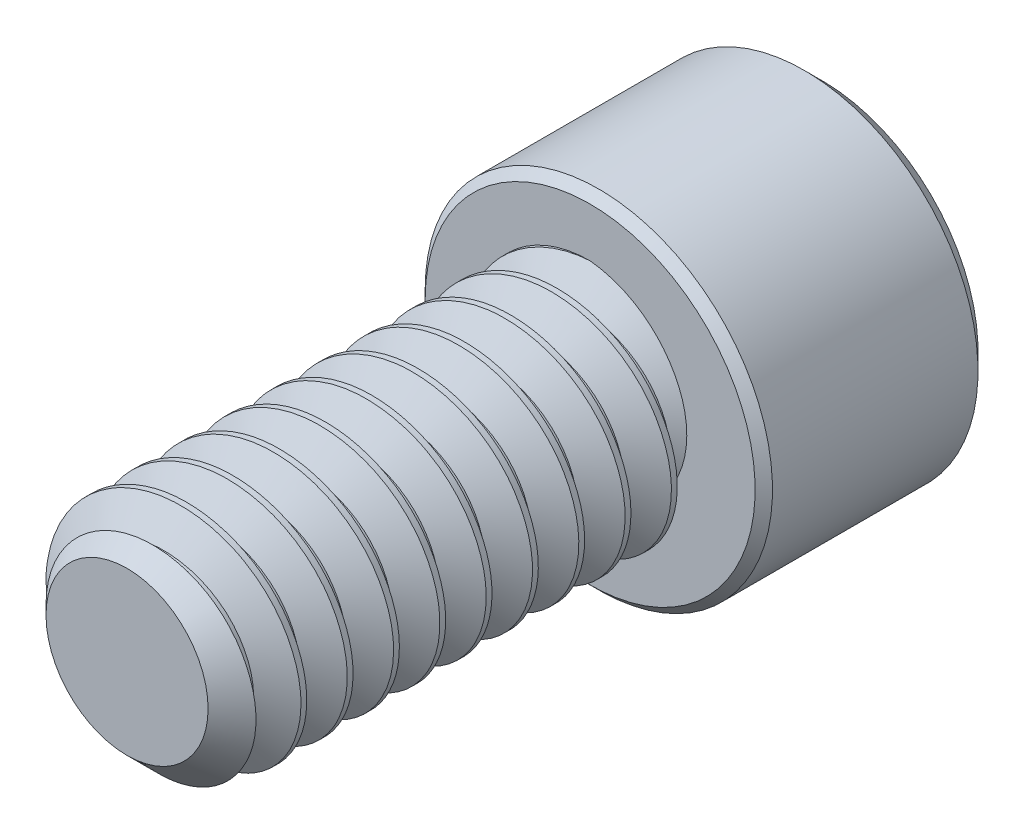
SolidWorks part; units mm, degrees
ref_plane "Front Plane" through (0, 0, 0) normal (0, 0, 1) x (1, 0, 0)
ref_plane "Top Plane" through (0, 0, 0) normal (0, 1, 0) x (1, 0, 0)
ref_plane "Right Plane" through (0, 0, 0) normal (1, 0, 0) x (0, 0, -1)
sketch "Sketch0" plane through (0, 0, 0) normal (1, 0, 0) x (0, 0, -1)
  line L0 (0, 0) -> (12.7, 0) construction
  point P2 (19.05, 0)
  point P4 (0, 0)
  dimension "D1" = 12.7
  dimension "D2" = 6.35
  dimension "Min Thread" = 0
sketch "Sketch1" plane through (0, 0, 0) normal (0, 0, 1) x (1, 0, 0)
  circle A0 centre (0, 0) radius 3.175
  dimension "OD" = 6.35
extrude "Extrude1" add sketch "Sketch1" against normal blind 12.7
sketch "Sketch2" plane through (0, 0, 0) normal (0, 0, 1) x (1, 0, 0)
  circle A0 centre (0, 0) radius 3.175 construction
  circle A1 centre (0, 0) radius 3.175
curve "Helix/Spiral1" pitch 1.27 height 13.97 turns 11 parameters "pitch"=1.27
chamfer "Chamfer3" distance 0.9525 angle 45 1 edges at (3.175, 0, 0)
sketch "Sketch3" plane through (0, 0, 0) normal (1, 0, 0) x (0, 0, -1)
  line L0 (-1.1113, 3.175) -> (-0.635, 2.3501)
  line L1 (-0.635, 2.3501) -> (-0.4763, 2.3501)
  line L2 (-0.4763, 2.3501) -> (0, 3.175)
  line L3 (-1.1113, 3.175) -> (0, 3.175)
  line L4 (-0.5556, 3.175) -> (-0.5556, 2.3501) construction
  line L5 (-0.8731, 2.7626) -> (-0.2381, 2.7626) construction
  line L6 (0, 3.175) -> (0, -3.175) construction
  dimension "D1" = 0.1588
  dimension "D2" = 0.635
  dimension "D3" = 60
sweep "Cut-Sweep1" cut profiles "Sketch3" path "Helix/Spiral1"
sketch "Sketch5" plane through (0, 0, 0) normal (1, 0, 0) x (0, 0, -1)
  line L0 (12.7, -2.3728) -> (12.7, 2.2654) construction
  line L1 (12.7, 3.175) -> (0, 3.175)
  line L2 (12.7, 3.175) -> (12.7, 0)
  line L3 (12.7, 0) -> (-1.1556, 0)
  line L4 (0, 0) -> (12.7, 0) construction
  line L5 (0, 3.175) -> (-1.1556, 0)
  line L6 (0, 0) -> (15.24, 0) construction
  dimension "D1" = 70
  dimension "D3" = 2.54
revolve "partially thread" [suppressed] add sketch "Sketch5" angle 360 about L6
sketch "Sketch6" plane through (0, 0, -12.7) normal (0, 0, -1) x (-1, 0, 0)
  circle A0 centre (0, 0) radius 4.7625
  dimension "head dia" = 9.525
extrude "Extrude2" add sketch "Sketch6" along normal blind 6.35
sketch "Sketch7" plane through (0, 0, -19.05) normal (0, 0, -1) x (-1, 0, 0)
  line L1 (0, 2.7496) -> (-2.3813, 1.3748)
  line L2 (-2.3813, 1.3748) -> (-2.3813, -1.3748)
  line L3 (-2.3813, -1.3748) -> (0, -2.7496)
  line L4 (0, -2.7496) -> (2.3813, -1.3748)
  line L5 (2.3813, -1.3748) -> (2.3813, 1.3748)
  line L6 (2.3813, 1.3748) -> (0, 2.7496)
  circle A0 centre (0, 0) radius 2.3813 construction
  dimension "hex dia" = 4.7625
extrude "Cut-Extrude1" cut sketch "Sketch7" against normal blind 3.5719
sketch "Sketch8" plane through (0, 0, -19.05) normal (0, 0, -1) x (-1, 0, 0)
  circle A0 centre (0, 0) radius 2.7496
extrude "Cut-Extrude2" cut sketch "Sketch8" against normal through all draft 45
chamfer "Chamfer1" distance 0.4763 angle 45 1 edges at (-4.7625, 0, -19.05)
chamfer "Chamfer2" distance 0.2381 angle 45 1 edges at (-4.7625, 0, -12.7)
sketch "Sketch9" plane through (0, 0, 0) normal (1, 0, 0) x (0, 0, -1)
  line L0 (0, 3.175) -> (0, -3.175) construction
  line L1 (3.175, 3.175) -> (3.175, -3.175) construction
  line L2 (19.05, 4.7625) -> (19.05, -4.7625) construction
  line L3 (12.7, 4.7625) -> (12.7, -4.7625) construction
  line L4 (12.7, 4.5244) -> (12.7, -4.5244) construction
  line L5 (19.05, -4.2862) -> (19.05, 4.2862) construction
  line L6 (12.7, -4.7625) -> (12.7, 4.7625) construction
  line L7 (0, 2.2225) -> (0, -2.2225) construction
  line L8 (-1.1113, 3.175) -> (0, 3.175) construction
  line L9 (3.175, 0) -> (0, 0) construction
  dimension "D1" = 3.175
equation "\"D3@Helix/Spiral1\" = \"screw length@Extrude1\"+\"pitch@Helix/Spiral1\""
equation "\"D1@Sketch3\" = \"pitch@Helix/Spiral1\"*.125"
equation "\"D2@Sketch3\" = \"pitch@Helix/Spiral1\"*.5"
equation "\"D1@Cut-Extrude1\" = \"hex dia@Sketch7\"*.75"
equation "\"D1@Chamfer1\" = \"head dia@Sketch6\"*.05"
equation "\"D1@Sketch9\" = \"pitch@Helix/Spiral1\"*2.50"
equation "\"D1@Chamfer2\" = \"D1@Chamfer1\"/2"
equation "\"D1@Chamfer3\" = \"pitch@Helix/Spiral1\"*.750"
equation "\"D1@Sketch0\" = \"screw length@Extrude1\""
equation "\"D2@Sketch0\" = \"head depth@Extrude2\""
